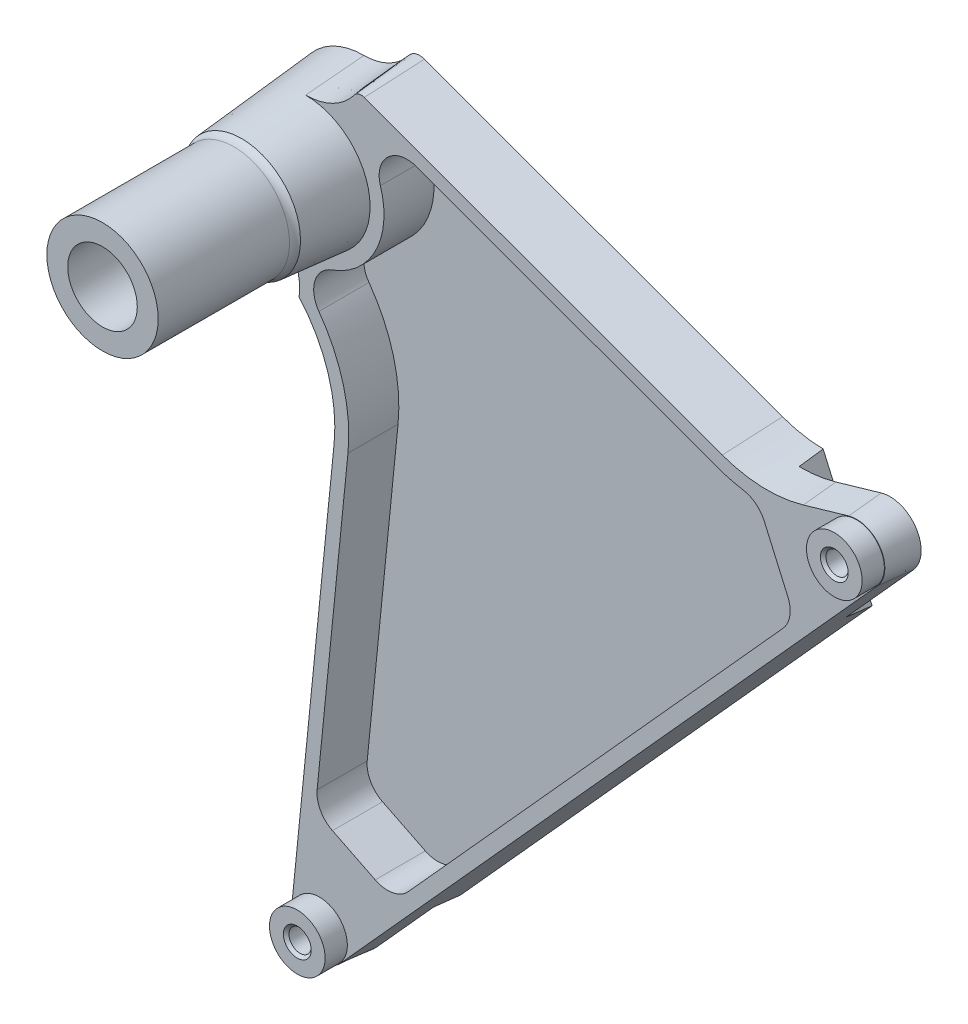
SolidWorks part; units mm, degrees
ref_plane "Спереди" through (0, 0, 0) normal (0, 0, 1) x (1, 0, 0)
ref_plane "Сверху" through (0, 0, 0) normal (0, 1, 0) x (1, 0, 0)
ref_plane "Справа" through (0, 0, 0) normal (1, 0, 0) x (0, 0, -1)
sketch "Эскиз1" plane through (0, 0, 0) normal (0, 0, 1) x (1, 0, 0)
  line L0 (0, 0) -> (0, -279.4414) construction
  line L1 (0, 0) -> (220.368, 0) construction
  line L2 (206.9028, -28.0377) -> (13.9104, -241.9843)
  line L3 (194.6432, -8.4769) -> (178.3526, -13.2118)
  line L4 (150.3602, -12.2709) -> (21.7148, 34.6968)
  line L5 (0, 0) -> (0, 112.2854) construction
  line L6 (-6.9398, -232.7466) -> (8.4118, -80)
  arc A0 (0, 25) -> (-13.3333, -21.1476) centre (0, 0) ccw
  arc A1 (-6.9398, -232.7466) -> (13.9104, -241.9843) centre (5, -233.9466) ccw
  arc A2 (206.9028, -28.0377) -> (194.6432, -8.4769) centre (197.9924, -20) ccw
  arc A3 (178.3526, -13.2118) -> (150.3602, -12.2709) centre (165.793, 30) cw
  arc A4 (0, 25) -> (16, 33) centre (0, 45) ccw
  arc A5 (21.7148, 34.6968) -> (16, 33) centre (20, 30) ccw
  arc A6 (8.4118, -80) -> (-4.2846, -41.428) centre (-41.3376, -75) ccw
  arc A7 (-4.2846, -41.428) -> (-13.3333, -21.1476) centre (-24, -38.0657) ccw
  dimension "D1" = 5
  dimension "D3" = 20
  dimension "D5" = 45
  dimension "D7" = 30
  dimension "D8" = 80
  dimension "D9" = 24
  dimension "D10" = 75
  dimension "D2" = 234
  dimension "D4" = 199
  dimension "D6" = 50
extrude "Основа детали" add sketch "Эскиз1" along normal blind 21 draft 5
sketch "Эскиз2" plane through (0, 0, 21) normal (0, 0, 1) x (1, 0, 0)
  circle A0 centre (5, -233.9466) radius 10
  circle A1 centre (197.9924, -20) radius 10
  arc A2 (-5.1118, -232.9303) -> (12.5462, -240.7537) centre (5, -233.9466) ccw construction
  arc A3 (205.5386, -26.8071) -> (195.156, -10.2411) centre (197.9924, -20) ccw construction
extrude "Малые бобышки" add sketch "Эскиз2" along normal blind 8
sketch "Эскиз3" plane through (0, 0, 0) normal (0, 0, -1) x (-1, 0, 0)
  line L2 (-13.9104, -241.9843) -> (-206.9028, -28.0377) construction
  line L4 (-164.9924, -14.9929) -> (-182.5812, -55)
  line L5 (-182.5812, -55) -> (-206.9028, -28.0377)
  line L6 (-164.9924, -14.9929) -> (-195.4068, -8.2819)
  line L9 (-8.4118, -80) -> (6.9398, -232.7466) construction
  line L10 (3.6433, -199.9466) -> (-34.6918, -218.9466)
  line L11 (-13.9104, -241.9843) -> (-34.6918, -218.9466)
  line L12 (3.6433, -199.9466) -> (6.9398, -232.7466)
  arc A0 (-195.4068, -8.2819) -> (-206.9028, -28.0377) centre (-197.9924, -20) ccw
  arc A1 (-194.6432, -8.4769) -> (-206.9028, -28.0377) centre (-197.9924, -20) ccw construction
  arc A4 (-178.3526, -13.2118) -> (-150.3602, -12.2709) centre (-165.793, 30) ccw construction
  arc A5 (-13.9104, -241.9843) -> (6.9398, -232.7466) centre (-5, -233.9466) ccw
  arc A6 (-13.9104, -241.9843) -> (6.9398, -232.7466) centre (-5, -233.9466) ccw construction
  point P6 (-182.5812, -55)
  point P7 (-164.9924, -14.9929)
  point P29 (-34.6918, -218.9466)
  point P30 (3.6433, -199.9466)
  dimension "D1" = 35
  dimension "D2" = 33
  dimension "D4" = 15
  dimension "D5" = 34
extrude "Боковые вырезы" cut sketch "Эскиз3" against normal blind 9
sketch "Эскиз4" plane through (0, 0, 21) normal (0, 0, 1) x (1, 0, 0)
  circle A0 centre (0, 0) radius 23.1627
  arc A1 (0, 23.1627) -> (-12.3535, -19.5935) centre (0, 0) ccw construction
extrude "Большая бобышка" add sketch "Эскиз4" along normal blind 23 draft 5
sketch "Эскиз5" plane through (0, 0, 44) normal (0, 0, 1) x (1, 0, 0)
  circle A0 centre (0, 0) radius 20
extrude "Надстройка большой бобышки" add sketch "Эскиз5" along normal blind 50
fillet "Скругление между большой бобышкой и надстройкой" radius 4 1 edges at (20, 0, 44)
sketch "Эскиз6" plane through (0, 0, 94) normal (0, 0, 1) x (1, 0, 0)
  circle A0 centre (0, 0) radius 12.5
extrude "Несквозной вырез большой бобышки" cut sketch "Эскиз6" against normal blind 24
sketch "Эскиз7" plane through (0, 0, 70) normal (0, 0, 1) x (1, 0, 0)
  circle A0 centre (0, 0) radius 10
extrude "Сквозной вырез большой бобышки" cut sketch "Эскиз7" against normal through all
fillet "Скругление между вырезами в большой бобышке" radius 0.3 1 edges at (10, 0, 70)
sketch "Эскиз8" plane through (0, 0, 29) normal (0, 0, 1) x (1, 0, 0)
  circle A0 centre (197.9924, -20) radius 4
  circle A1 centre (197.9924, -20) radius 10 construction
  circle A2 centre (5, -233.9466) radius 4
  circle A3 centre (5, -233.9466) radius 10 construction
extrude "Вырезы в малых бобышках" cut sketch "Эскиз8" against normal through all
chamfer "Фаски в вырезах малых бобышек" distance 1 angle 45 2 edges at (9, -233.9466, 29) (201.9924, -20, 29)
sketch "Эскиз11" plane through (0, 0, 21) normal (0, 0, 1) x (1, 0, 0)
  line L30 (-0.6691, -195.8402) -> (36.1794, -214.1034)
  line L31 (9.6378, -200.9486) -> (25.0172, -208.5711)
  line L32 (15.2147, -80.6837) -> (-0.1369, -233.4303)
  line L33 (8.8335, -237.4046) -> (201.8259, -23.458)
  line L34 (196.5515, -15.0424) -> (180.2609, -19.7773)
  line L35 (148.0153, -18.6935) -> (20.6167, 27.819)
  line L36 (15.2147, -80.6837) -> (4.1287, -190.9888)
  line L37 (36.8833, -206.3093) -> (171.5599, -57.0102)
  line L39 (148.0153, -18.6935) -> (39.8485, 20.7976)
  line L41 (177.6566, -56.222) -> (160.7636, -17.7975)
  line L42 (173.289, -46.2874) -> (164.798, -26.974)
  arc A56 (25.0172, -208.5711) -> (36.8833, -206.3093) centre (29.458, -199.6112) ccw
  arc A57 (4.1287, -190.9888) -> (9.6378, -200.9486) centre (14.0785, -191.9888) ccw
  arc A58 (157.2849, -21.1343) -> (164.798, -26.974) centre (155.6436, -30.9987) cw
  arc A59 (173.289, -46.2874) -> (171.5599, -57.0102) centre (164.1346, -50.3121) cw
  arc A60 (39.8485, 20.7976) -> (26.8759, 8.4158) centre (36.419, 11.404) ccw
  arc A61 (9.5088, -26.5089) -> (4.7725, -41.7685) centre (12.8851, -35.9217) ccw
  arc A64 (15.8045, 23.31) -> (20.6167, 27.819) centre (0, 45) ccw
  arc A65 (0.9371, -28.1471) -> (15.8045, 23.31) centre (0, 0) ccw
  arc A66 (2.813, -39.2062) -> (0.9371, -28.1471) centre (-24, -38.0657) ccw
  arc A67 (15.2147, -80.6837) -> (2.813, -39.2062) centre (-41.3376, -75) ccw
  arc A68 (-0.1369, -233.4303) -> (8.8335, -237.4046) centre (5, -233.9466) ccw
  arc A69 (201.8259, -23.458) -> (196.5515, -15.0424) centre (197.9924, -20) ccw
  arc A70 (148.0153, -18.6935) -> (180.2609, -19.7773) centre (165.793, 30) ccw
  arc A72 (9.5088, -26.5089) -> (26.8759, 8.4158) centre (0, 0) ccw
  arc A74 (15.2147, -80.6837) -> (4.7725, -41.7685) centre (-41.3376, -75) ccw
  arc A77 (148.0153, -18.6935) -> (157.2849, -21.1343) centre (165.793, 30) ccw
  dimension "D3" = 10
  dimension "D4" = 10
  dimension "D6" = 10
  dimension "D7" = 10
  dimension "D1" = 5
  dimension "D2" = 5
  dimension "D5" = 5
extrude "Вырез в основе центральный" cut sketch "Эскиз11" against normal blind 18
